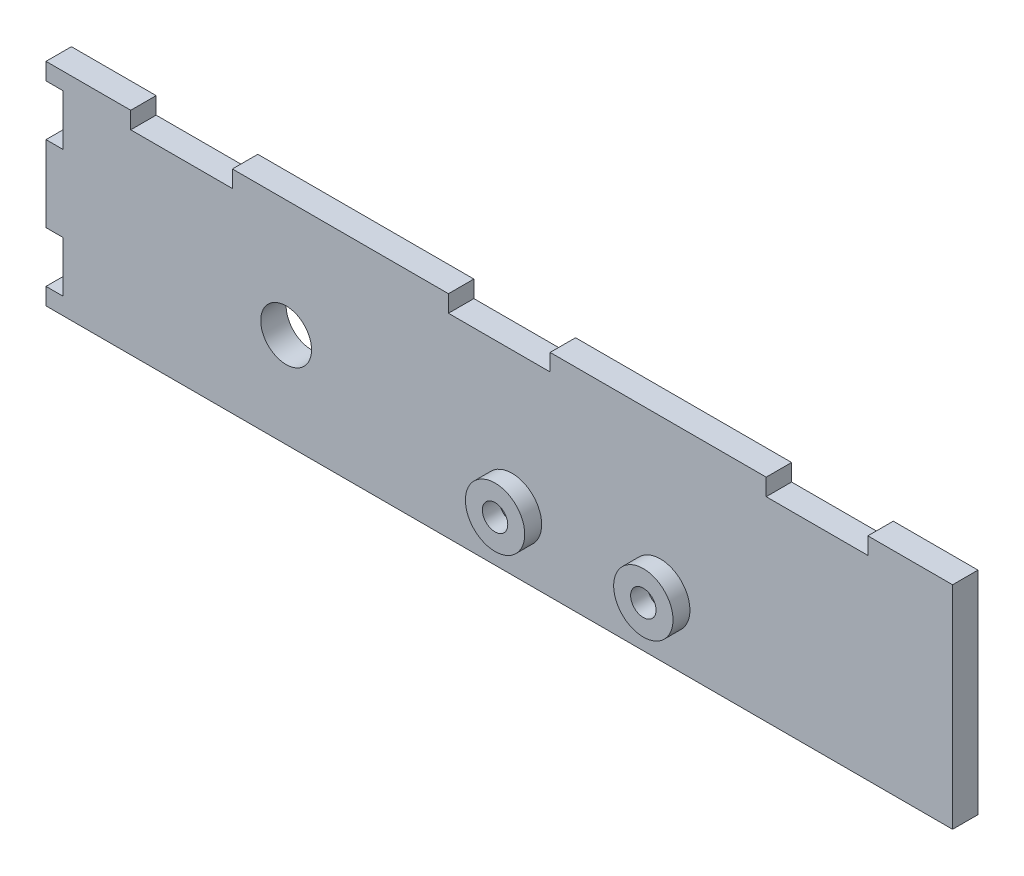
SolidWorks part; units mm, degrees
note: The reader was unsure of these and kept them because the rebuilt part matched: shared geometry of "Esboço1<19>", "Esboço1<20>".
ref_plane "Plano frontal" through (0, 0, 0) normal (0, 0, 1) x (1, 0, 0)
ref_plane "Plano superior" through (0, 0, 0) normal (0, 1, 0) x (1, 0, 0)
ref_plane "Plano direito" through (0, 0, 0) normal (1, 0, 0) x (0, 0, -1)
sketch "Esboço1" plane through (0, 0, 0) normal (0, 0, 1) x (1, 0, 0)
  line L1 (-40.6777, 33.2717) -> (66.3223, 33.2717)
  line L2 (-40.6777, 33.2717) -> (-40.6777, 8.2717)
  line L3 (-40.6777, 8.2717) -> (66.3223, 8.2717)
  line L4 (66.3223, 33.2717) -> (66.3223, 8.2717)
  line L6 (66.3223, 31.2717) -> (-40.6777, 31.2717)
  line L7 (-38.6777, 31.2717) -> (-38.6777, 8.2717)
  line L8 (56.3223, 33.2717) -> (44.3223, 33.2717)
  line L9 (56.3223, 33.2717) -> (56.3223, 31.2717)
  line L10 (56.3223, 31.2717) -> (44.3223, 31.2717)
  line L11 (44.3223, 33.2717) -> (44.3223, 31.2717)
  line L12 (-30.6777, 33.2717) -> (-18.6777, 33.2717)
  line L13 (-30.6777, 33.2717) -> (-30.6777, 31.2717)
  line L14 (-30.6777, 31.2717) -> (-18.6777, 31.2717)
  line L15 (-18.6777, 33.2717) -> (-18.6777, 31.2717)
  line L16 (-38.6777, 16.2717) -> (-40.6777, 16.2717)
  line L17 (-38.6777, 31.2717) -> (-40.6777, 31.2717)
  line L18 (-38.6777, 31.2717) -> (-38.6777, 25.2717)
  line L19 (-38.6777, 25.2717) -> (-40.6777, 25.2717)
  line L20 (-40.6777, 31.2717) -> (-40.6777, 25.2717)
  line L21 (-38.6777, 10.2717) -> (-40.6777, 10.2717)
  line L23 (18.8223, 33.2717) -> (6.8223, 33.2717)
  line L24 (18.8223, 33.2717) -> (18.8223, 31.2717)
  line L25 (18.8223, 31.2717) -> (6.8223, 31.2717)
  line L26 (6.8223, 33.2717) -> (6.8223, 31.2717)
  circle A0 centre (14.3223, 15.1717) radius 1.5
  circle A1 centre (31.8223, 15.1717) radius 1.5
  circle A3 centre (14.3223, 15.1717) radius 3.5
  circle A4 centre (31.8223, 15.1717) radius 3.5
  circle A6 centre (49.3223, 15.1717) radius 1.5 [skipped]
  circle A7 centre (49.3223, 15.1717) radius 3.5 [skipped]
  circle A9 centre (-12.3361, 19.4528) radius 3
  point P4 (14.3223, 8.2717)
  point P5 (14.3223, 8.2717)
  point P51 (12.8223, 33.2717)
  dimension "D4" = 3
  dimension "D7" = 7
  dimension "D19" = 6
  dimension "D1" = 107
  dimension "D2" = 25
  dimension "D3" = 55
  dimension "D5" = 6.9
  dimension "D6" = 3
  dimension "D9" = 17.5
  dimension "D10" = 17.5
  dimension "D20" = 27
  dimension "D21" = 2
  dimension "D22" = 10
  dimension "D23" = 12
  dimension "D24" = 12
  dimension "D25" = 10
  dimension "D26" = 2
  dimension "D27" = 6
  dimension "D28" = 2
  dimension "D29" = 6
  dimension "D30" = 6
  dimension "D31" = 6
  dimension "D8" = 3
extrude "Ressalto-extrusão1" add sketch "Esboço1" along normal blind 3 contours L6 L7 L3 L4 A9 A4 A3 | L13 L1 L2 L6 | L26 L1 L15 L6 | L1 L24 L6 L11 | L1 L9 L6 L4 | L7 L19 L2 L16 | L7 L21 L2 L3 | A3 A0 | A4 A1
extrude "Ressalto-extrusão2" add sketch "Esboço1<19>" along normal blind 5 contours A3 | A4 | A0 | A1
sketch "Esboço1<19>" plane through (0, 0, 0) normal (0, 0, 1) x (1, 0, 0) same geometry as "Esboço1"
extrude "Ressalto-extrusão3" add sketch "Esboço1<20>" along normal blind 3 contours A1 | A0
sketch "Esboço1<20>" plane through (0, 0, 0) normal (0, 0, 1) x (1, 0, 0) same geometry as "Esboço1"
